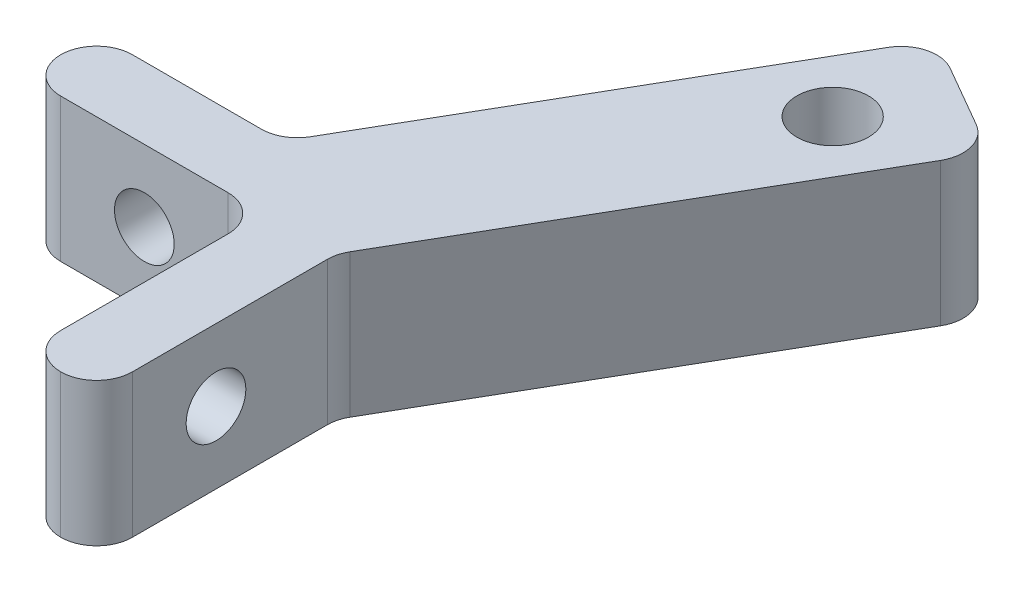
SolidWorks part; units mm, degrees
material "6061 Alloy"
ref_plane "Front Plane" through (0, 0, 0) normal (0, 0, 1) x (1, 0, 0)
ref_plane "Top Plane" through (0, 0, 0) normal (0, 1, 0) x (1, 0, 0)
ref_plane "Right Plane" through (0, 0, 0) normal (1, 0, 0) x (0, 0, -1)
sketch "Sketch1" plane through (0, 0, 0) normal (0, 1, 0) x (1, 0, 0)
  line L0 (0, 0) -> (-15.5366, 0)
  line L1 (-15.5366, 0) -> (-15.5366, -6)
  line L2 (-15.5366, -6) -> (4.4634, -6)
  line L3 (4.4634, -6) -> (4.4634, -26)
  line L4 (4.4634, -26) -> (10.4634, -26)
  line L5 (10.4634, -26) -> (10.4634, -5.8769)
  line L6 (10.4634, -5.8769) -> (30.4634, 28.7641)
  line L7 (30.4634, 28.7641) -> (20.0711, 34.7641)
  line L8 (20.0711, 34.7641) -> (2.632, 4.5588)
  line L9 (2.632, 4.5588) -> (0, 0)
  line L10 (25.2672, 31.7641) -> (21.2672, 24.8359) construction
  circle A0 centre (21.2672, 24.8359) radius 3
  dimension "D11" = 6
  dimension "D1" = 6
  dimension "D2" = 6
  dimension "D3" = 20
  dimension "D4" = 20
  dimension "D5" = 12
  dimension "D6" = 12
  dimension "D7" = 120
  dimension "D8" = 90
  dimension "D9" = 40
  dimension "D10" = 5.264
  dimension "D12" = 8
extrude "Boss-Extrude1" add sketch "Sketch1" along normal blind 6 and the other way blind 6
sketch "Sketch2" plane through (4.4634, 0, 0) normal (-1, 0, 0) x (0, 0, 1)
  line L0 (6, 6) -> (26, -6) construction
  circle A0 centre (16, 0) radius 2.5
  dimension "D1" = 5
extrude "Cut-Extrude1" cut sketch "Sketch2" against normal through all
sketch "Sketch3" plane through (0, 0, 6) normal (0, 0, 1) x (1, 0, 0)
  line L0 (4.4634, -6) -> (-15.5366, 6) construction
  circle A0 centre (-5.5366, 0) radius 2.5
  dimension "D1" = 5
extrude "Cut-Extrude2" cut sketch "Sketch3" against normal through all
fillet "Fillet1" radius 3 9 edges at (10.4634, 0, 26) (4.4634, 0, 26) (-15.5366, 0, 6) (-15.5366, 0, 0) (4.4634, 0, 6) (10.4634, 0, 5.8769) (30.4634, 0, -28.7641) (20.0711, 0, -34.7641) (0, 0, 0)
